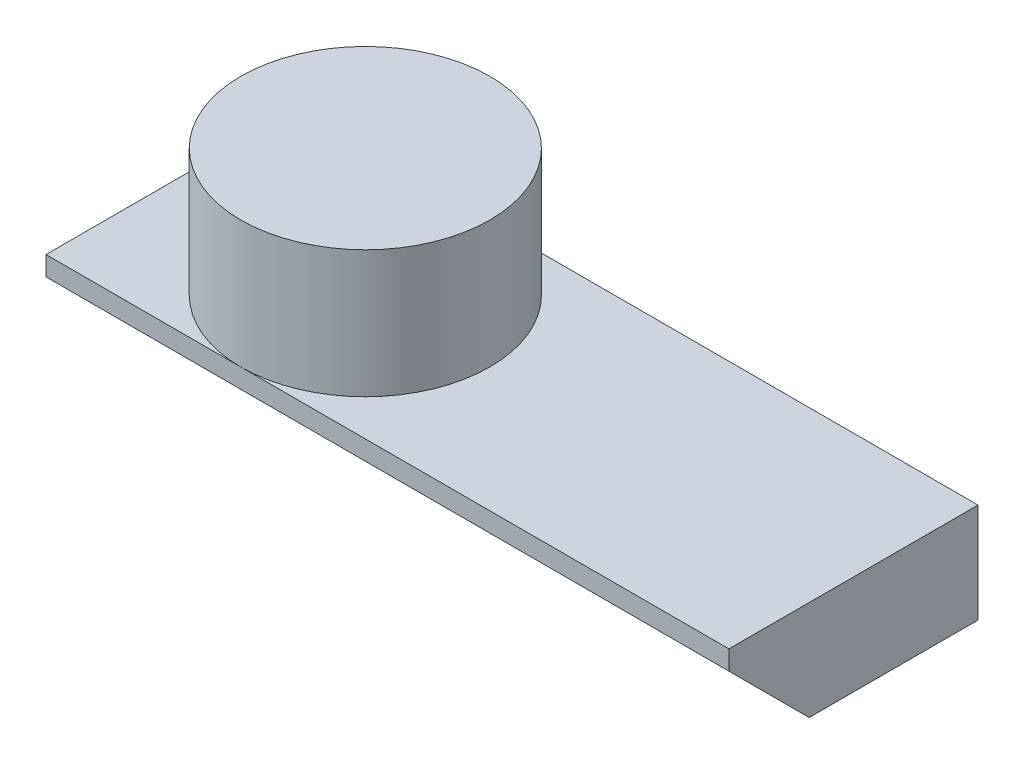
SolidWorks part; units mm, degrees
ref_plane "Front" through (0, 0, 0) normal (0, 0, 1) x (1, 0, 0)
ref_plane "Top" through (0, 0, 0) normal (0, 1, 0) x (1, 0, 0)
ref_plane "Right" through (0, 0, 0) normal (1, 0, 0) x (0, 0, -1)
sketch "Sketch1" plane through (0, 0, 0) normal (0, 1, 0) x (1, 0, 0)
  circle A0 centre (0, 0) radius 2.25
  dimension "D1" = 4.5
extrude "Boss-Extrude1" add sketch "Sketch1" along normal blind 1.15 and the other way blind 1.15
sketch "Sketch2" plane through (0, -1.15, 0) normal (0, -1, 0) x (1, 0, 0)
  line L1 (-3.52, 2.25) -> (3.52, 2.25)
  line L2 (-3.52, 2.25) -> (-3.52, -2.25)
  line L3 (-3.52, -2.25) -> (3.52, -2.25)
  line L5 (3.52, 2.25) -> (8.82, 2.25)
  line L7 (3.52, -2.25) -> (8.82, -2.25)
  line L8 (8.82, 2.25) -> (8.82, -2.25)
  point P0 (0, 0)
  dimension "D1" = 4.5
  dimension "D2" = 7.04
  dimension "D3" = 5.3
extrude "Boss-Extrude2" add sketch "Sketch2" along normal blind 1.8
chamfer "Chamfer2" distance 1.45 angle 45 1 edges at (2.65, -2.95, 2.25)
chamfer "Chamfer4" distance 1.45 angle 45 1 edges at (-3.52, -2.95, -0.725)
